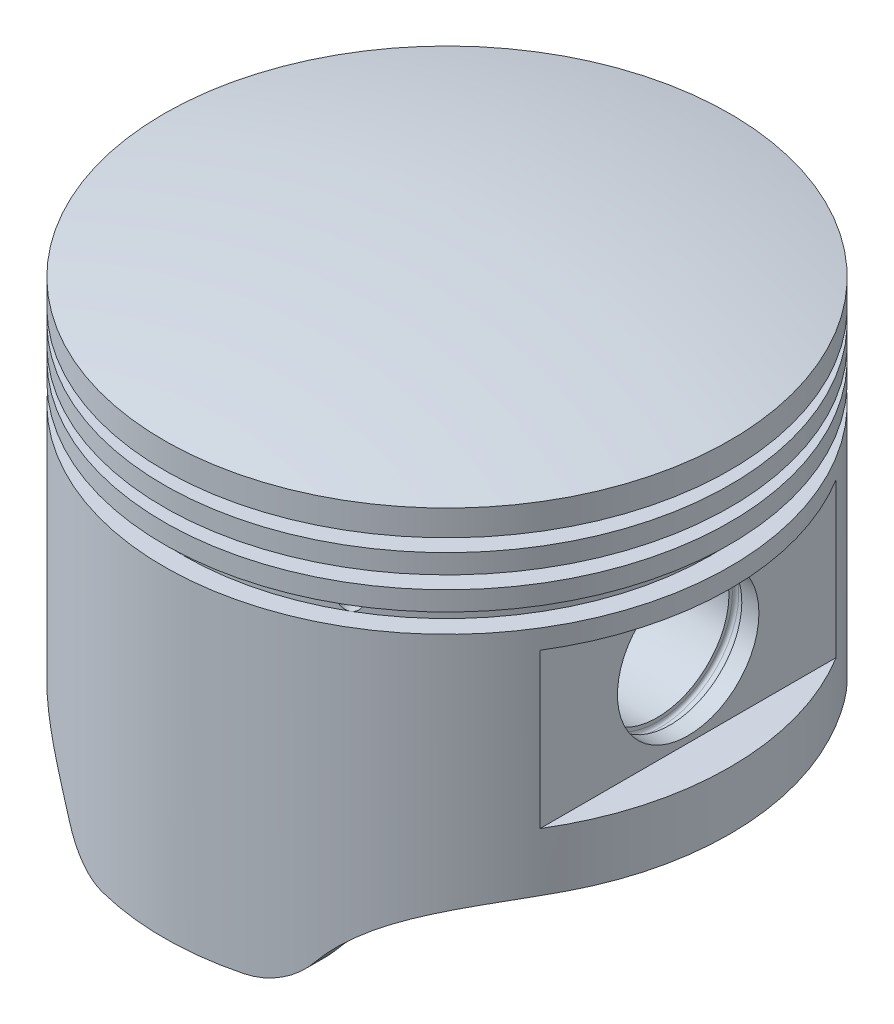
SolidWorks part; units mm, degrees
ref_plane "Front Plane" through (0, 0, 0) normal (0, 0, 1) x (1, 0, 0)
ref_plane "Top Plane" through (0, 0, 0) normal (0, 1, 0) x (1, 0, 0)
ref_plane "Right Plane" through (0, 0, 0) normal (1, 0, 0) x (0, 0, -1)
sketch "Sketch1" plane through (0, 0, 0) normal (0, 0, 1) x (1, 0, 0)
  line L0 (41, 0) -> (44, 0)
  line L1 (44, 0) -> (44, 50)
  line L2 (44, 67) -> (0, 67)
  line L3 (0, 67) -> (0, 59)
  line L4 (0, 59) -> (36, 59)
  line L5 (36, 59) -> (36, 20)
  line L6 (36, 20) -> (41, 20)
  line L7 (41, 20) -> (41, 0)
  line L8 (0, 59) -> (0, 0) construction
  line L9 (0, 0) -> (41, 0) construction
  line L10 (44, 63) -> (44, 67)
  line L11 (44, 63) -> (41, 63)
  line L13 (44, 61) -> (41, 61)
  line L14 (41, 63) -> (41, 61)
  line L15 (44, 58) -> (41, 58)
  line L17 (44, 56) -> (41, 56)
  line L18 (41, 58) -> (41, 56)
  line L19 (44, 53) -> (41, 53)
  line L21 (44, 50) -> (41, 50)
  line L22 (41, 53) -> (41, 50)
  line L23 (44, 58) -> (44, 61)
  line L24 (44, 53) -> (44, 56)
  dimension "D1" = 44
  dimension "D2" = 20
  dimension "D3" = 8
  dimension "D4" = 39
  dimension "D5" = 3
  dimension "D6" = 8
  dimension "D7" = 4
  dimension "D8" = 3
  dimension "D9" = 3
  dimension "D10" = 2
  dimension "D11" = 2
  dimension "D12" = 3
  dimension "D13" = 3
revolve "Revolve1" add sketch "Sketch1" angle 360 about L8
sketch "Sketch2" plane through (0, 0, 0) normal (0, 0, 1) x (1, 0, 0)
  line L0 (0, 0) -> (0, 38.9985) construction
  line L1 (-44, 50) -> (-44, 0) construction
  line L2 (-37.5, 23) -> (-50.5, 23)
  line L3 (-37.5, 23) -> (-37.5, 47)
  line L4 (-37.5, 47) -> (-50.5, 47)
  line L5 (-50.5, 23) -> (-50.5, 47)
  line L6 (-37.5, 23) -> (-50.5, 47) construction
  line L7 (-37.5, 47) -> (-50.5, 23) construction
  line L8 (37.5, 47) -> (50.5, 47)
  line L9 (50.5, 23) -> (50.5, 47)
  line L10 (37.5, 23) -> (50.5, 23)
  line L11 (37.5, 23) -> (37.5, 47)
  line L12 (44, 67) -> (-44, 67) construction
  point P3 (-44, 35)
  dimension "D1" = 24
  dimension "D2" = 13
  dimension "D3" = 20
extrude "Cut-Extrude1" cut sketch "Sketch2" against normal through all both and the other way through all
sketch "Sketch3" plane through (0, 59, 0) normal (0, -1, 0) x (1, 0, 0)
  line L1 (-30, 19.8997) -> (30, 19.8997)
  line L2 (-30, 19.8997) -> (-30, -19.8997)
  line L3 (-30, -19.8997) -> (30, -19.8997)
  line L4 (30, 19.8997) -> (30, -19.8997)
  line L5 (-30, 19.8997) -> (30, -19.8997) construction
  line L6 (-30, -19.8997) -> (30, 19.8997) construction
  circle A1 centre (0, 0) radius 36
  circle A2 centre (0, 0) radius 36
  circle M6 centre (0, 0) radius 36
  dimension "D2" = 30
  dimension "D1" = 0
extrude "Boss-Extrude1" add sketch "Sketch3" along normal up to surface (39 mm away) contours L2 M6 | L4 M6 region at (-32.418, 59, 0) region at (32.418, 59, 0) up to face at (-41, 20, 0)
sketch "Sketch5" plane through (-30, 0, 0) normal (1, 0, 0) x (0, 0, -1)
  line L0 (0, 59) -> (0, 35) construction
  line L1 (-19.8997, 59) -> (19.8997, 59) construction
  line L2 (15, 59) -> (15, 35)
  line L3 (-15, 59) -> (-15, 35)
  line L4 (19.8997, 20) -> (-19.8997, 20) construction
  line L5 (-19.8997, 59) -> (19.8997, 59)
  arc A0 (15, 59) -> (-15, 59) centre (0, 59) ccw
  arc A1 (-15, 35) -> (15, 35) centre (0, 35) ccw
  point P5 (0, 47)
  line M7 (19.8997, 59) -> (-19.8997, 59)
  dimension "D1" = 15
extrude "Boss-Extrude2" add sketch "Sketch5" along normal blind 10 contours L3 A1 L2 L5 M7 region at (-30, 40.9529, 0)
mirror "Mirror1" about plane through (0, 0, 0) normal (1, 0, 0) of "Boss-Extrude2"
sketch "Sketch6" plane through (37.5, 0, 0) normal (1, 0, 0) x (0, 0, -1)
  line L0 (-23.0163, 47) -> (23.0163, 23) construction
  circle A0 centre (0, 35) radius 11
  dimension "D1" = 22
extrude "Cut-Extrude2" cut sketch "Sketch6" against normal through all
fillet "Fillet1" radius 2 6 edges at (-20, 47, 15) (-20, 47, -15) (20, 47, 15) (20, 47, -15) (-20, 20, 0) (20, 20, 0)
dome "Dome1" faces to dome 1 distance 5 reverse direction no elliptical dome no face at (-44, 67, 0) parameters "D1"=5
sketch "Sketch7" plane through (0, 0, 0) normal (0, 0, 1) x (1, 0, 0)
  line L0 (-44, 0) -> (-44, 14)
  line L1 (-44, 23) -> (-44, 0) construction
  line L2 (-44, 14) -> (-39, 14)
  line L3 (-44, 0) -> (44, 0) construction
  line L4 (-44, 0) -> (-16.5501, 0)
  line L5 (-37.5, 23) -> (-44, 23) construction
  line L6 (0, 0) -> (0, 34.5445) construction
  line L7 (44, 0) -> (16.5501, 0)
  line L8 (44, 14) -> (39, 14)
  line L9 (44, 0) -> (44, 14)
  arc A0 (-39, 14) -> (-16.5501, 0) centre (-39, -11) cw
  arc A1 (39, 14) -> (16.5501, 0) centre (39, -11) ccw
  dimension "D2" = 25
  dimension "D1" = 5
  dimension "D3" = 9
extrude "Cut-Extrude3" cut sketch "Sketch7" against normal through all both and the other way through all
fillet "Fillet2" radius 10 4 edges at (16.5501, 0, -39.14) (-16.5501, 0, -39.14) (-16.5501, 0, 39.14) (16.5501, 0, 39.14)
sketch "Sketch8" plane through (0, 0, 0) normal (0, 0, 1) x (1, 0, 0)
  line L0 (0, 0) -> (0, 73.0343) construction
  line L1 (30, 35) -> (0, 35.4501) construction
  line L2 (0, 35.4501) -> (0, 50.3932) construction
  line L3 (37.5, 46) -> (20, 46) construction
  line L4 (33.5, 47) -> (34.5, 47)
  line L5 (33, 46.5) -> (33, 45.5)
  line L6 (33.5, 45) -> (34.5, 45)
  line L7 (35, 46.5) -> (35, 45.5)
  line L8 (33, 47) -> (35, 45) construction
  line L9 (33, 45) -> (35, 47) construction
  line L10 (-33, 45) -> (-35, 47) construction
  line L11 (-33, 47) -> (-35, 45) construction
  line L12 (-35, 46.5) -> (-35, 45.5)
  line L13 (-33.5, 45) -> (-34.5, 45)
  line L14 (-33, 46.5) -> (-33, 45.5)
  line L15 (-33.5, 47) -> (-34.5, 47)
  arc A0 (34.5, 47) -> (35, 46.5) centre (34.5, 46.5) cw
  arc A1 (34.5, 45) -> (35, 45.5) centre (34.5, 45.5) ccw
  arc A2 (33, 45.5) -> (33.5, 45) centre (33.5, 45.5) ccw
  arc A3 (33.5, 47) -> (33, 46.5) centre (33.5, 46.5) ccw
  arc A4 (-33.5, 47) -> (-33, 46.5) centre (-33.5, 46.5) cw
  arc A5 (-33, 45.5) -> (-33.5, 45) centre (-33.5, 45.5) cw
  arc A6 (-34.5, 45) -> (-35, 45.5) centre (-34.5, 45.5) cw
  arc A7 (-34.5, 47) -> (-35, 46.5) centre (-34.5, 46.5) ccw
  point P6 (34, 46)
  point P42 (-34, 46)
  dimension "D4" = 0.5
  dimension "D1" = 2
  dimension "D2" = 2
  dimension "D3" = 34
revolve "Cut-Revolve1" cut sketch "Sketch8" angle 360 about L1
sketch "Sketch9" plane through (0, 0, 0) normal (0, 0, 1) x (1, 0, 0)
  line L0 (0, 50) -> (0, 53) construction
  line L1 (44, 50) -> (-44, 50) construction
  line L2 (-41, 53) -> (41, 53) construction
  circle A0 centre (0, 51.5) radius 1.5
extrude "Cut-Extrude5" cut sketch "Sketch9" against normal through all
pattern_circular "CirPattern1" count 12 over 360 about axis through (0, 50, 0) along (0, 1, 0) skipping 2, 3, 4, 8, 9, 10 of "Cut-Extrude5"
